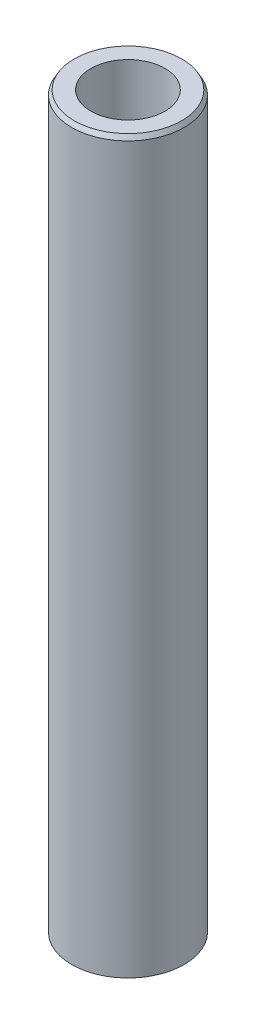
SolidWorks part; units mm, degrees
ref_plane "Front Plane" through (0, 0, 0) normal (0, 0, 1) x (1, 0, 0)
ref_plane "Top Plane" through (0, 0, 0) normal (0, 1, 0) x (1, 0, 0)
ref_plane "Right Plane" through (0, 0, 0) normal (1, 0, 0) x (0, 0, -1)
sketch "Sketch1" plane through (0, 0, 0) normal (0, 1, 0) x (1, 0, 0)
  circle A0 centre (0, 0) radius 17.5
  dimension "SHAFT_OD" = 35
extrude "Boss-Extrude1" add sketch "Sketch1" along normal blind 227.6628
sketch "Sketch2" plane through (0, 0, 0) normal (0, 1, 0) x (1, 0, 0)
  circle A0 centre (0, 0) radius 11.5244
  dimension "BORE_D" = 23.0488
extrude "Cut-Extrude1" cut sketch "Sketch2" along normal through all
chamfer "Chamfer1" distance 1.4026 angle 30 2 edges at (0, 227.6628, 17.5) (0, 0, 17.5) first distance on face at (0, 227.6628, 17.5) first distance on face at (0, 0, 11.5244)
